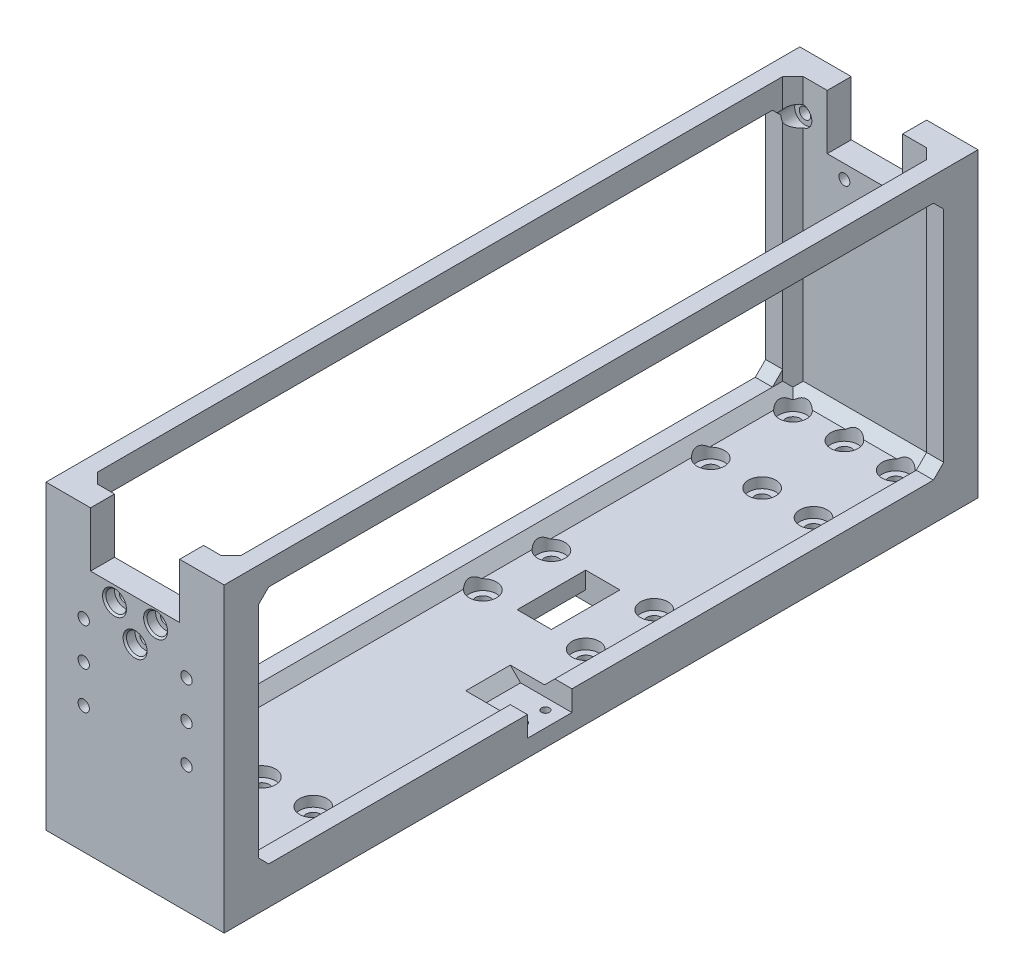
SolidWorks part; units mm, degrees
ref_plane "Front Plane" through (0, 0, 0) normal (0, 0, 1) x (1, 0, 0)
ref_plane "Top Plane" through (0, 0, 0) normal (0, 1, 0) x (1, 0, 0)
ref_plane "Right Plane" through (0, 0, 0) normal (1, 0, 0) x (0, 0, -1)
sketch "Sketch1" plane through (0, 0, 0) normal (0, 1, 0) x (1, 0, 0)
  line L1 (7.7612, 52.9422) -> (59.7612, 52.9422)
  line L2 (7.7612, 52.9422) -> (7.7612, -167.0578)
  line L3 (7.7612, -167.0578) -> (59.7612, -167.0578)
  line L4 (59.7612, 52.9422) -> (59.7612, -167.0578)
  dimension "D1" = 52
  dimension "D2" = 220
extrude "Boss-Extrude1" add sketch "Sketch1" along normal blind 8
sketch "Sketch2" plane through (0, 8, 0) normal (0, 1, 0) x (1, 0, 0)
  line L0 (7.7612, -167.0578) -> (59.7612, -167.0578) construction
  line L1 (7.7612, 52.9422) -> (12.7612, 52.9422)
  line L2 (7.7612, 52.9422) -> (7.7612, -167.0578)
  line L3 (7.7612, -167.0578) -> (12.7612, -167.0578)
  line L4 (12.7612, 52.9422) -> (12.7612, -167.0578)
  dimension "D1" = 5
extrude "Boss-Extrude2" add sketch "Sketch2" along normal blind 80
sketch "Sketch3" plane through (0, 8, 0) normal (0, 1, 0) x (1, 0, 0)
  line L0 (12.7612, -167.0578) -> (12.7612, 52.9422) construction
  line L1 (59.7612, -167.0578) -> (12.7612, -167.0578)
  line L2 (59.7612, -167.0578) -> (59.7612, -160.0578)
  line L3 (59.7612, -160.0578) -> (12.7612, -160.0578)
  line L4 (12.7612, -167.0578) -> (12.7612, -160.0578)
  dimension "D1" = 7
extrude "Boss-Extrude3" add sketch "Sketch3" along normal blind 80
sketch "Sketch4" plane through (0, 8, 0) normal (0, 1, 0) x (1, 0, 0)
  line L0 (12.7612, -160.0578) -> (12.7612, 52.9422) construction
  line L1 (59.7612, 52.9422) -> (12.7612, 52.9422)
  line L2 (59.7612, 52.9422) -> (59.7612, 45.9422)
  line L3 (59.7612, 45.9422) -> (12.7612, 45.9422)
  line L4 (12.7612, 52.9422) -> (12.7612, 45.9422)
  dimension "D1" = 7
extrude "Boss-Extrude4" add sketch "Sketch4" along normal blind 80
sketch "Sketch8" plane through (7.7612, 0, 0) normal (-1, 0, 0) x (0, 0, 1)
  line L0 (-52.9422, 88) -> (167.0578, 88) construction
  line L1 (-42.9422, 88) -> (157.0578, 88)
  line L2 (-42.9422, 88) -> (-42.9422, 8)
  line L3 (-42.9422, 8) -> (157.0578, 8)
  line L4 (157.0578, 88) -> (157.0578, 8)
  line L5 (-52.9422, 88) -> (-52.9422, 0) construction
  line L6 (167.0578, 88) -> (167.0578, 0) construction
  line L7 (-52.9422, 0) -> (167.0578, 0) construction
  dimension "D1" = 0
  dimension "D2" = 10
  dimension "D3" = 10
  dimension "D4" = 8
extrude "Cut-Extrude3" cut sketch "Sketch8" against normal blind 10
sketch "Sketch12" plane through (0, 8, 0) normal (0, 1, 0) x (1, 0, 0)
  line L0 (12.7612, 45.9422) -> (59.7612, 45.9422) construction
  line L1 (59.7612, -160.0578) -> (54.7612, -160.0578)
  line L2 (59.7612, -160.0578) -> (59.7612, 45.9422)
  line L3 (59.7612, 45.9422) -> (54.7612, 45.9422)
  line L4 (54.7612, -160.0578) -> (54.7612, 45.9422)
  line L6 (7.7612, -157.0578) -> (12.7612, -157.0578)
  line L7 (7.7612, -157.0578) -> (7.7612, 42.9422)
  line L8 (7.7612, 42.9422) -> (12.7612, 42.9422)
  line L9 (12.7612, -157.0578) -> (12.7612, 42.9422)
  dimension "D1" = 5
extrude "Boss-Extrude6" add sketch "Sketch12" along normal blind 3
sketch "Sketch13" plane through (0, 88, 0) normal (0, 1, 0) x (1, 0, 0)
  line L0 (54.7612, 45.9422) -> (54.7612, -160.0578) construction
  line L1 (59.7612, -160.0578) -> (54.7612, -160.0578)
  line L2 (59.7612, -160.0578) -> (59.7612, -157.0578)
  line L3 (59.7612, -157.0578) -> (54.7612, -157.0578)
  line L4 (54.7612, -160.0578) -> (54.7612, -157.0578)
  line L6 (59.7612, 45.9422) -> (54.7612, 45.9422)
  line L7 (59.7612, 45.9422) -> (59.7612, 42.9422)
  line L8 (59.7612, 42.9422) -> (54.7612, 42.9422)
  line L9 (54.7612, 45.9422) -> (54.7612, 42.9422)
  dimension "D1" = 3
  dimension "D2" = 3
extrude "Boss-Extrude7" add sketch "Sketch13" against normal up to surface (77 mm away) up to face at (57.2612, 11, 57.0578)
sketch "Sketch15" plane through (0, 0, -45.9422) normal (0, 0, 1) x (1, 0, 0)
  line L0 (12.7612, 88) -> (54.7612, 88) construction
  line L1 (7.7612, 88) -> (7.7612, 0) construction
  circle A0 centre (18.7612, 68) radius 3
  circle A1 centre (48.7612, 68) radius 3
  dimension "D1" = 6
  dimension "D2" = 6
  dimension "D3" = 20
  dimension "D4" = 20
  dimension "D5" = 11
  dimension "D6" = 41
sketch "Sketch19" plane through (0, 0, -42.9422) normal (0, 0, 1) x (1, 0, 0)
  line L0 (12.7612, 88) -> (12.7612, 11) construction
  line L1 (7.7612, 88) -> (12.7612, 88)
  line L2 (7.7612, 88) -> (7.7612, 81)
  line L3 (7.7612, 81) -> (12.7612, 81)
  line L4 (12.7612, 88) -> (12.7612, 81)
  line L5 (59.7612, 11) -> (59.7612, 88) construction
  line L6 (54.7612, 88) -> (59.7612, 88)
  line L7 (54.7612, 88) -> (54.7612, 81)
  line L8 (54.7612, 81) -> (59.7612, 81)
  line L9 (59.7612, 88) -> (59.7612, 81)
  dimension "D1" = 7
  dimension "D2" = 7
extrude "Boss-Extrude11" add sketch "Sketch19" along normal up to surface (200 mm away) up to face at (10.2612, 49.5, 157.0578)
sketch "Sketch21" plane through (0, 0, 167.0578) normal (0, 0, 1) x (1, 0, 0)
  circle A0 centre (18.7612, 59) radius 1.65
  circle A1 centre (48.7612, 59) radius 1.65
  circle A2 centre (48.7612, 37) radius 1.65
  circle A3 centre (18.7612, 37) radius 1.65
extrude "Cut-Extrude10" cut sketch "Sketch21" against normal blind 10
sketch "Sketch22" plane through (0, 0, 160.0578) normal (0, 0, -1) x (-1, 0, 0)
  circle A0 centre (-18.7612, 59) radius 3
  circle A1 centre (-48.7612, 59) radius 3
  circle A2 centre (-18.7612, 37) radius 3
  circle A3 centre (-48.7612, 37) radius 3
  dimension "D1" = 6
  dimension "D2" = 6
  dimension "D3" = 6
  dimension "D4" = 6
extrude "Cut-Extrude11" cut sketch "Sketch22" against normal blind 2
sketch "Sketch23" plane through (0, 0, 167.0578) normal (0, 0, 1) x (1, 0, 0)
  circle A0 centre (18.7612, 48) radius 1.65
  circle A1 centre (48.7612, 48) radius 1.65
extrude "Cut-Extrude12" cut sketch "Sketch23" against normal blind 10
sketch "Sketch24" plane through (0, 0, 160.0578) normal (0, 0, -1) x (-1, 0, 0)
  circle A0 centre (-48.7612, 48) radius 3
  circle A1 centre (-18.7612, 48) radius 3
  dimension "D1" = 6
  dimension "D2" = 6
extrude "Cut-Extrude13" cut sketch "Sketch24" against normal blind 2
sketch "Sketch25" plane through (0, 88, 0) normal (0, 1, 0) x (1, 0, 0)
  line L0 (7.7612, -167.0578) -> (59.7612, -167.0578) construction
  line L1 (46.7612, -167.0578) -> (20.7612, -167.0578)
  line L2 (46.7612, -167.0578) -> (46.7612, -160.0578)
  line L3 (46.7612, -160.0578) -> (20.7612, -160.0578)
  line L4 (20.7612, -167.0578) -> (20.7612, -160.0578)
  line L5 (54.7612, -160.0578) -> (12.7612, -160.0578) construction
  line L6 (7.7612, 52.9422) -> (7.7612, -167.0578) construction
  line L7 (59.7612, -167.0578) -> (59.7612, 52.9422) construction
  dimension "D1" = 13
  dimension "D2" = 13
extrude "Cut-Extrude14" cut sketch "Sketch25" against normal blind 16
sketch "Sketch26" plane through (0, 88, 0) normal (0, 1, 0) x (1, 0, 0)
  line L0 (59.7612, 52.9422) -> (7.7612, 52.9422) construction
  line L1 (44.7612, 52.9422) -> (22.7612, 52.9422)
  line L2 (44.7612, 52.9422) -> (44.7612, 45.9422)
  line L3 (44.7612, 45.9422) -> (22.7612, 45.9422)
  line L4 (22.7612, 52.9422) -> (22.7612, 45.9422)
  line L5 (12.7612, 45.9422) -> (54.7612, 45.9422) construction
  line L6 (7.7612, 52.9422) -> (7.7612, -167.0578) construction
  line L7 (59.7612, -167.0578) -> (59.7612, 52.9422) construction
  dimension "D1" = 15
  dimension "D2" = 15
extrude "Cut-Extrude15" cut sketch "Sketch26" against normal blind 16
sketch "Sketch32" plane through (0, 0, -52.9422) normal (0, 0, -1) x (-1, 0, 0)
  circle A0 centre (-52.2612, 78) radius 1.65
  circle A1 centre (-15.2612, 78) radius 1.65
extrude "Cut-Extrude18" cut sketch "Sketch32" against normal blind 10
sketch "Sketch33" plane through (0, 0, -42.9422) normal (0, 0, 1) x (1, 0, 0)
  circle A0 centre (15.2612, 78) radius 3
  circle A1 centre (52.2612, 78) radius 3
  dimension "D1" = 6
  dimension "D2" = 6
extrude "Cut-Extrude19" cut sketch "Sketch33" against normal blind 4
chamfer "Chamfer5" distance 3 angle 45 4 edges at (57.2612, 81, -42.9422) (10.2612, 81, -42.9422) (10.2612, 81, 157.0578) (57.2612, 81, 157.0578)
sketch "Sketch49" plane through (0, 0, 160.0578) normal (0, 0, -1) x (-1, 0, 0)
  circle A0 centre (-18.7612, 68) radius 3
  circle A1 centre (-48.7612, 68) radius 3
  dimension "D1" = 6
  dimension "D2" = 6
chamfer "Chamfer12" distance 3 angle 45 4 edges at (12.7612, 42.1708, -45.9422) (12.7612, 83.8292, -45.9422) (54.7612, 42.1708, -45.9422) (54.7612, 83.8292, -45.9422)
chamfer "Chamfer16" distance 3 angle 45 2 edges at (12.7612, 48, 160.0578) (54.7612, 48, 160.0578)
chamfer "Chamfer18" distance 3 angle 45 3 edges at (12.7612, 8, 57.0578) (33.7612, 8, 160.0578) (54.7612, 8, 57.0578)
chamfer "Chamfer21" distance 3 angle 45 1 edges at (33.7612, 8, -45.9422)
sketch "Sketch53" plane through (0, 0, 0) normal (0, -1, 0) x (1, 0, 0)
  line L0 (7.7612, 167.0578) -> (59.7612, 167.0578) construction
  line L1 (59.7612, 167.0578) -> (59.7612, -52.9422) construction
  line L2 (7.7612, -52.9422) -> (7.7612, 167.0578) construction
  line L3 (59.7612, -52.9422) -> (7.7612, -52.9422) construction
  circle A0 centre (48.7612, 154.0578) radius 2.15
  circle A1 centre (18.7612, 154.0578) radius 2.15
  circle A2 centre (18.7612, 130.0578) radius 2.15
  circle A3 centre (48.7612, 130.0578) radius 2.15
  circle A4 centre (48.7612, -15.9422) radius 2.15
  circle A5 centre (48.7612, -39.9422) radius 2.15
  circle A6 centre (18.7612, -15.9422) radius 2.15
  circle A7 centre (18.7612, -39.9422) radius 2.15
  dimension "D1" = 4.3
  dimension "D2" = 4.3
  dimension "D3" = 4.3
  dimension "D4" = 4.3
  dimension "D5" = 4.3
  dimension "D6" = 4.3
  dimension "D7" = 4.3
  dimension "D8" = 4.3
  dimension "D9" = 13
  dimension "D10" = 13
  dimension "D11" = 37
  dimension "D12" = 37
  dimension "D13" = 11
  dimension "D14" = 11
  dimension "D15" = 11
  dimension "D16" = 11
  dimension "D17" = 13
  dimension "D18" = 13
  dimension "D19" = 37
  dimension "D20" = 37
  dimension "D21" = 11
  dimension "D22" = 11
  dimension "D23" = 11
  dimension "D24" = 11
extrude "Cut-Extrude31" cut sketch "Sketch53" against normal up to surface (11 mm away) up to face at (10.2612, 11, 57.0578)
sketch "Sketch54" plane through (0, 0, 0) normal (0, -1, 0) x (1, 0, 0)
  line L0 (7.7612, 167.0578) -> (59.7612, 167.0578) construction
  line L1 (59.7612, 167.0578) -> (59.7612, -52.9422) construction
  line L2 (59.7612, -52.9422) -> (7.7612, -52.9422) construction
  circle A0 centre (33.7612, 154.0578) radius 2.15
  circle A1 centre (33.7612, 130.0578) radius 2.15
  circle A2 centre (33.7612, -15.9422) radius 2.15
  circle A3 centre (33.7612, -39.9422) radius 2.15
  dimension "D1" = 4.3
  dimension "D2" = 4.3
  dimension "D3" = 4.3
  dimension "D4" = 4.3
  dimension "D5" = 13
  dimension "D6" = 37
  dimension "D7" = 26
  dimension "D8" = 26
  dimension "D9" = 13
  dimension "D10" = 37
  dimension "D11" = 26
  dimension "D12" = 26
extrude "Cut-Extrude32" cut sketch "Sketch54" against normal up to surface (11 mm away) up to face at (57.2612, 11, 57.0578)
sketch "Sketch55" plane through (0, 11, 0) normal (0, 1, 0) x (1, 0, 0)
  circle A0 centre (18.7612, -130.0578) radius 4
  circle A1 centre (18.7612, -154.0578) radius 4
  circle A2 centre (48.7612, -130.0578) radius 4
  circle A3 centre (48.7612, -154.0578) radius 4
  circle A4 centre (33.7612, -130.0578) radius 4
  circle A5 centre (33.7612, -154.0578) radius 4
  circle A6 centre (48.7612, 15.9422) radius 4
  circle A7 centre (33.7612, 15.9422) radius 4
  circle A8 centre (18.7612, 15.9422) radius 4
  circle A9 centre (18.7612, 39.9422) radius 4
  circle A10 centre (33.7612, 39.9422) radius 4
  circle A11 centre (48.7612, 39.9422) radius 4
  dimension "D1" = 8
  dimension "D2" = 8
  dimension "D3" = 8
  dimension "D4" = 8
  dimension "D5" = 8
  dimension "D6" = 8
  dimension "D7" = 8
  dimension "D8" = 8
  dimension "D9" = 8
  dimension "D10" = 8
  dimension "D11" = 8
  dimension "D12" = 8
extrude "Cut-Extrude33" cut sketch "Sketch55" against normal blind 6
sketch "Sketch56" plane through (0, 0, 0) normal (0, -1, 0) x (1, 0, 0)
  line L0 (59.7612, -52.9422) -> (7.7612, -52.9422) construction
  line L1 (7.7612, -52.9422) -> (7.7612, 167.0578) construction
  line L2 (59.7612, 167.0578) -> (59.7612, -52.9422) construction
  circle A0 centre (18.7612, 30.5578) radius 2.15
  circle A1 centre (18.7612, 50.5578) radius 2.15
  circle A2 centre (48.7612, 30.5578) radius 2.15
  circle A3 centre (48.7612, 50.5578) radius 2.15
  dimension "D1" = 4.3
  dimension "D2" = 4.3
  dimension "D3" = 4.3
  dimension "D4" = 4.3
  dimension "D5" = 83.5
  dimension "D6" = 83.5
  dimension "D7" = 103.5
  dimension "D8" = 103.5
  dimension "D9" = 11
  dimension "D10" = 11
  dimension "D11" = 11
  dimension "D12" = 11
extrude "Cut-Extrude34" cut sketch "Sketch56" against normal up to surface (11 mm away) up to face at (57.2612, 11, 57.0578)
sketch "Sketch57" plane through (0, 11, 0) normal (0, 1, 0) x (1, 0, 0)
  circle A0 centre (48.7612, -30.5578) radius 4
  circle A1 centre (48.7612, -50.5578) radius 4
  circle A2 centre (18.7612, -30.5578) radius 4
  circle A3 centre (18.7612, -50.5578) radius 4
  dimension "D1" = 8
  dimension "D2" = 8
  dimension "D3" = 8
  dimension "D4" = 8
extrude "Cut-Extrude35" cut sketch "Sketch57" against normal blind 6
sketch "Sketch58" plane through (0, 8, 0) normal (0, 1, 0) x (1, 0, 0)
  line L0 (59.7612, -167.0578) -> (59.7612, 52.9422) construction
  line L1 (38.7612, -30.5578) -> (28.7612, -30.5578)
  line L2 (38.7612, -30.5578) -> (38.7612, -50.5578)
  line L3 (38.7612, -50.5578) -> (28.7612, -50.5578)
  line L4 (28.7612, -30.5578) -> (28.7612, -50.5578)
  line L5 (59.7612, 52.9422) -> (44.7612, 52.9422) construction
  dimension "D1" = 10
  dimension "D2" = 21
  dimension "D3" = 20
  dimension "D4" = 83.5
extrude "Cut-Extrude36" cut sketch "Sketch58" against normal up to surface (8 mm away) up to face at (18.7612, 0, 48.4078)
chamfer "Chamfer22" distance 3 angle 45 2 edges at (28.7612, 0, 40.5578) (38.7612, 0, 40.5578)
sketch "Sketch59" plane through (0, 11, 0) normal (0, 1, 0) x (1, 0, 0)
  line L0 (54.7612, 42.9422) -> (54.7612, -157.0578) construction
  line L1 (59.7612, -157.0578) -> (54.7612, -157.0578)
  line L2 (59.7612, -157.0578) -> (59.7612, -154.0578)
  line L3 (59.7612, -154.0578) -> (54.7612, -154.0578)
  line L4 (54.7612, -157.0578) -> (54.7612, -154.0578)
  line L5 (12.7612, -157.0578) -> (12.7612, 42.9422) construction
  line L6 (7.7612, -157.0578) -> (12.7612, -157.0578)
  line L7 (7.7612, -157.0578) -> (7.7612, -154.0578)
  line L8 (7.7612, -154.0578) -> (12.7612, -154.0578)
  line L9 (12.7612, -157.0578) -> (12.7612, -154.0578)
  line L11 (7.7612, 42.9422) -> (12.7612, 42.9422)
  line L12 (7.7612, 42.9422) -> (7.7612, 39.9422)
  line L13 (7.7612, 39.9422) -> (12.7612, 39.9422)
  line L14 (12.7612, 42.9422) -> (12.7612, 39.9422)
  line L15 (59.7612, 42.9422) -> (54.7612, 42.9422)
  line L16 (59.7612, 42.9422) -> (59.7612, 39.9422)
  line L17 (59.7612, 39.9422) -> (54.7612, 39.9422)
  line L18 (54.7612, 42.9422) -> (54.7612, 39.9422)
  dimension "D1" = 3
  dimension "D2" = 3
  dimension "D3" = 3
  dimension "D4" = 3
extrude "Boss-Extrude21" add sketch "Sketch59" along normal blind 3
chamfer "Chamfer24" distance 3 angle 45 4 edges at (57.2612, 14, -39.9422) (10.2612, 14, -39.9422) (10.2612, 14, 154.0578) (57.2612, 14, 154.0578)
sketch "Sketch76" plane through (0, 0, 160.0578) normal (0, 0, -1) x (-1, 0, 0)
  line L0 (-54.7612, 14) -> (-54.7612, 78) construction
  circle A0 centre (-33.7612, 60) radius 1.6
  circle A4 centre (-48.7612, 68) radius 3 construction
  circle A5 centre (-18.7612, 68) radius 3 construction
  circle A6 centre (-39.7612, 68) radius 1.6
  circle A7 centre (-27.7526, 67.608) radius 1.6
  dimension "D1" = 3.2
  dimension "D3" = 21
  dimension "D5" = 8
  dimension "D7" = 3.2
  dimension "D8" = 9
  dimension "D9" = 8
  dimension "D10" = 3.2
  dimension "D11" = 9
extrude "Cut-Extrude46" cut sketch "Sketch76" against normal up to surface (7 mm away) up to face at (33.7612, 62, 167.0578)
sketch "Sketch77" plane through (0, 0, 167.0578) normal (0, 0, 1) x (1, 0, 0)
  circle A0 centre (39.7612, 68) radius 3
  circle A1 centre (33.7612, 60) radius 3
  circle A3 centre (27.7526, 67.608) radius 3
  dimension "D1" = 6
  dimension "D2" = 6
  dimension "D3" = 6
extrude "Cut-Extrude48" cut sketch "Sketch77" against normal blind 3
chamfer "Chamfer27" distance 0.5 angle 45 3 edges at (42.7612, 68, 167.0578) (36.7612, 60, 167.0578) (30.7526, 67.608, 167.0578)
sketch "Sketch78" plane through (0, 0, -45.9422) normal (0, 0, 1) x (1, 0, 0)
  line L0 (12.7612, 76.3417) -> (12.7612, 14) construction
  circle A0 centre (27.7612, 68) radius 1.6
  circle A1 centre (39.7612, 68) radius 1.6
  circle A2 centre (33.7612, 60) radius 1.6
  circle A3 centre (18.7612, 68) radius 3 construction
  circle A4 centre (48.7612, 68) radius 3 construction
  dimension "D1" = 3.2
  dimension "D2" = 3.2
  dimension "D3" = 3.2
  dimension "D4" = 8
  dimension "D5" = 21
  dimension "D6" = 8
  dimension "D7" = 8
  dimension "D8" = 9
  dimension "D9" = 9
extrude "Cut-Extrude49" cut sketch "Sketch78" against normal up to surface (7 mm away) up to face at (50.6112, 78, -52.9422)
sketch "Sketch79" plane through (0, 0, -52.9422) normal (0, 0, -1) x (-1, 0, 0)
  circle A0 centre (-39.7612, 68) radius 3
  circle A1 centre (-27.7612, 68) radius 3
  circle A2 centre (-33.7612, 60) radius 3
  dimension "D1" = 6
  dimension "D2" = 6
  dimension "D3" = 6
extrude "Cut-Extrude50" cut sketch "Sketch79" against normal blind 3
chamfer "Chamfer28" distance 0.5 angle 45 3 edges at (30.7612, 60, -52.9422) (24.7612, 68, -52.9422) (36.7612, 68, -52.9422)
sketch "Sketch80" plane through (0, 11, 0) normal (0, 1, 0) x (1, 0, 0)
  line L0 (59.7612, -154.0578) -> (59.7612, 39.9422) construction
  line L1 (59.7612, -65.5578) -> (41.7612, -65.5578)
  line L2 (59.7612, -65.5578) -> (59.7612, -78.5578)
  line L3 (59.7612, -78.5578) -> (41.7612, -78.5578)
  line L4 (41.7612, -65.5578) -> (41.7612, -78.5578)
  line L5 (28.7612, -50.5578) -> (38.7612, -50.5578) construction
  dimension "D1" = 13
  dimension "D2" = 18
  dimension "D3" = 15
extrude "Cut-Extrude51" cut sketch "Sketch80" against normal blind 6
chamfer "Chamfer29" distance 3 angle 45 1 edges at (41.7612, 5, 72.0578)
sketch "Sketch81" plane through (0, 5, 0) normal (0, 1, 0) x (1, 0, 0)
  line L0 (59.7612, -65.5578) -> (44.7612, -65.5578) construction
  line L1 (44.7612, -78.5578) -> (59.7612, -78.5578) construction
  line L2 (59.7612, -78.5578) -> (59.7612, -65.5578) construction
  circle A0 centre (55.2612, -75.3078) radius 1.15
  circle A1 centre (55.2612, -68.8078) radius 1.15
  dimension "D1" = 2.3
  dimension "D2" = 2.3
  dimension "D3" = 3.25
  dimension "D4" = 3.25
  dimension "D5" = 4.5
  dimension "D6" = 4.5
extrude "Cut-Extrude52" cut sketch "Sketch81" against normal up to surface (5 mm away) up to face at (33.7612, 0, 40.5578)
